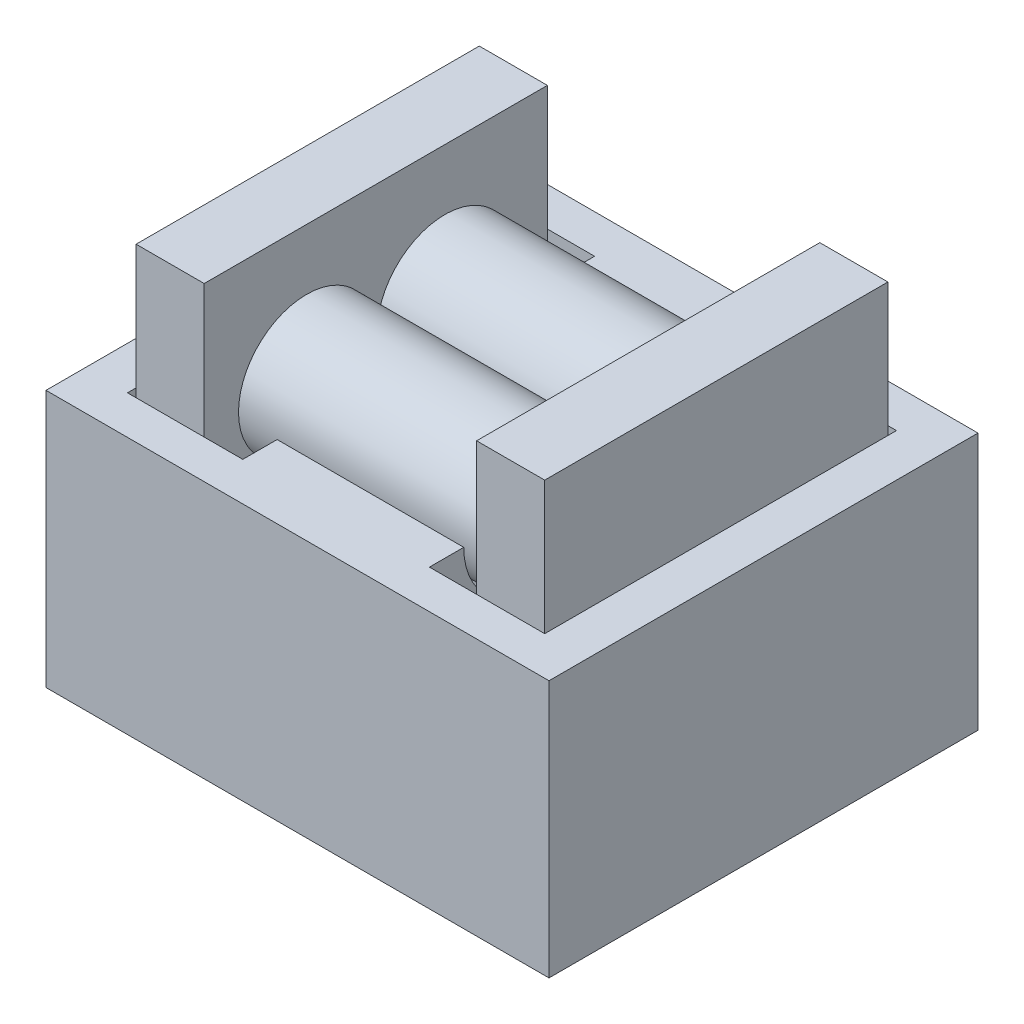
SolidWorks part; units mm, degrees
ref_plane "Front Plane" through (0, 0, 0) normal (0, 0, 1) x (1, 0, 0)
ref_plane "Top Plane" through (0, 0, 0) normal (0, 1, 0) x (1, 0, 0)
ref_plane "Right Plane" through (0, 0, 0) normal (1, 0, 0) x (0, 0, -1)
sketch "Sketch2" plane through (0, 0, 0) normal (0, 1, 0) x (1, 0, 0)
  line L1 (0, 0) -> (1.5875, 0)
  line L2 (0, 0) -> (0, 8)
  line L3 (0, 8) -> (1.5875, 8)
  line L4 (1.5875, 0) -> (1.5875, 8)
  dimension "D1" = 1.5875
  dimension "D2" = 8
extrude "Boss-Extrude1" add sketch "Sketch2" along normal blind 8
sketch "Sketch3" plane through (0, 0, 0) normal (-1, 0, 0) x (0, 0, 1)
  line L0 (-4, 8) -> (-4, 0) construction
  line L1 (-8, 8) -> (0, 8) construction
  line L2 (-8, 0) -> (0, 0) construction
  line L3 (-4.025, 5) -> (-3.975, 5) construction
  line L4 (-5.6125, 7.5) -> (-2.3875, 7.5) construction
  line L5 (-2.3875, 2.5) -> (-5.6125, 2.5) construction
  circle A0 centre (-5.6125, 5) radius 1.5875
  circle A1 centre (-2.3875, 5) radius 1.5875
  arc A2 (-5.6125, 2.5) -> (-5.6125, 7.5) centre (-5.6125, 5) cw construction
  arc A3 (-2.3875, 2.5) -> (-2.3875, 7.5) centre (-2.3875, 5) ccw construction
  point P12 (-4, 5)
  dimension "D1" = 3.175
  dimension "D4" = 5
  dimension "D2" = 0.05
  dimension "D3" = 0.5
extrude "Boss-Extrude2" add sketch "Sketch3" along normal blind 6.35
sketch "Sketch4" plane through (-6.35, 0, 0) normal (-1, 0, 0) x (0, 0, 1)
  line L0 (-8, 0) -> (0, 0) construction
  line L1 (-8, 8) -> (0, 8) construction
  line L2 (0, 8) -> (0, 0) construction
  line L3 (-8, 8) -> (-8, 0) construction
  line L4 (-8, 0) -> (0, 0)
  line L5 (-8, 8) -> (0, 8)
  line L6 (0, 8) -> (0, 0)
  line L7 (-8, 8) -> (-8, 0)
extrude "Boss-Extrude3" add sketch "Sketch4" along normal blind 1.5875
ref_plane "Plane1" through (-3.175, 0, 0) normal (-1, 0, 0) x (0, 0, 1)
sketch "Sketch5" plane through (-3.175, 0, 0) normal (-1, 0, 0) x (0, 0, 1)
  line L0 (-5.6125, 5) -> (-2.3875, 5) construction
  line L1 (-4, 5) -> (-4, 4.5025) construction
  line L2 (-7.3, 5) -> (-9, 5)
  line L3 (-0.7, 5) -> (1, 5)
  line L4 (-8, 0) -> (0, 0)
  line L5 (0, 0) -> (0, 8)
  line L6 (0, 8) -> (-8, 8)
  line L7 (-8, 8) -> (-8, 0)
  line L8 (-8, 0) -> (0, 0) construction
  line L9 (0, 0) -> (0, 8) construction
  line L10 (0, 8) -> (-8, 8) construction
  line L11 (-8, 8) -> (-8, 0) construction
  line L12 (1, 5) -> (1, 0)
  line L13 (1, 0) -> (-9, 0)
  line L14 (-9, 0) -> (-9, 5)
  circle A0 centre (-2.3875, 5) radius 1.5875 construction
  circle A1 centre (-2.3875, 5) radius 1.5875 construction
  circle A2 centre (-5.6125, 5) radius 1.5875 construction
  circle A3 centre (-5.6125, 5) radius 1.5875 construction
  arc A4 (-7.3, 5) -> (-4, 4.5025) centre (-5.6125, 5) ccw
  arc A5 (-0.7, 5) -> (-4, 4.5025) centre (-2.3875, 5) cw
  dimension "D2" = 0.1
  dimension "D3" = 1
  dimension "D1" = 0
extrude "Boss-Extrude4" add sketch "Sketch5" against normal offset from surface 1 and the other way offset from surface 1 separate body up to face at (0, 5, -3.975) other way up to face at (-6.35, 5, -4.025)
sketch "Sketch6" plane through (0, 0, 0) normal (0, -1, 0) x (1, 0, 0)
  line L0 (-1, 1) -> (-5.35, 1) construction
  line L1 (2.6875, -9) -> (-9.0375, -9)
  line L2 (2.6875, -9) -> (2.6875, 1)
  line L3 (2.6875, 1) -> (-9.0375, 1)
  line L4 (-9.0375, -9) -> (-9.0375, 1)
  line L5 (-1, -9) -> (-5.35, -9) construction
  line L6 (1.5875, -8) -> (0, -8) construction
  line L7 (0, -8) -> (0, 0) construction
  line L8 (0, 0) -> (1.5875, 0) construction
  line L9 (1.5875, 0) -> (1.5875, -8) construction
  line L10 (1.5875, -8) -> (0, -8) construction
  line L11 (0, -8) -> (0, 0) construction
  line L12 (0, 0) -> (1.5875, 0) construction
  line L13 (1.5875, 0) -> (1.5875, -8) construction
  line L14 (-6.35, -8) -> (-6.35, 0) construction
  line L15 (-7.9375, -8) -> (-6.35, -8) construction
  line L16 (-7.9375, -8) -> (-7.9375, 0) construction
  line L17 (-7.9375, 0) -> (-6.35, 0) construction
  line L18 (-7.9375, 0) -> (-6.35, 0) construction
  line L19 (-7.9375, -8) -> (-7.9375, 0) construction
  line L20 (-7.9375, -8) -> (-6.35, -8) construction
  line L21 (-6.35, -8) -> (-6.35, 0) construction
  line L22 (1.6875, -8.1) -> (-0.1, -8.1)
  line L23 (-0.1, -8.1) -> (-0.1, 0.1)
  line L24 (-0.1, 0.1) -> (1.6875, 0.1)
  line L25 (1.6875, 0.1) -> (1.6875, -8.1)
  line L26 (-8.0375, 0.1) -> (-6.25, 0.1)
  line L27 (-6.25, -8.1) -> (-6.25, 0.1)
  line L28 (-8.0375, -8.1) -> (-6.25, -8.1)
  line L29 (-8.0375, -8.1) -> (-8.0375, 0.1)
  point P24 (-3.175, 1)
  dimension "D3" = 1
  dimension "D1" = 0.1
  dimension "D2" = 0.1
extrude "Boss-Extrude5" add sketch "Sketch6" against normal blind 3
sketch "Sketch8" plane through (0, 3, 0) normal (0, 1, 0) x (1, 0, 0)
  line L1 (-8.0375, -0.1) -> (1.6875, -0.1)
  line L2 (-8.0375, -0.1) -> (-8.0375, 8.1)
  line L3 (-8.0375, 8.1) -> (1.6875, 8.1)
  line L4 (1.6875, -0.1) -> (1.6875, 8.1)
  line L5 (-9.0375, -1) -> (2.6875, -1)
  line L6 (-9.0375, -1) -> (-9.0375, 9)
  line L7 (-9.0375, 9) -> (2.6875, 9)
  line L8 (2.6875, -1) -> (2.6875, 9)
extrude "Boss-Extrude6" add sketch "Sketch8" along normal up to surface (2 mm away) up to face at (-3.175, 5, 0.15)
sketch "Sketch9" plane through (0, 0, 0) normal (0, -1, 0) x (1, 0, 0)
  line L1 (-9.0375, -9) -> (2.6875, -9)
  line L2 (-9.0375, -9) -> (-9.0375, 1)
  line L3 (-9.0375, 1) -> (2.6875, 1)
  line L4 (2.6875, -9) -> (2.6875, 1)
extrude "Boss-Extrude7" add sketch "Sketch9" along normal blind 1 separate body
combine bodies "Combine1" operation type add bodies to combine 106 107
